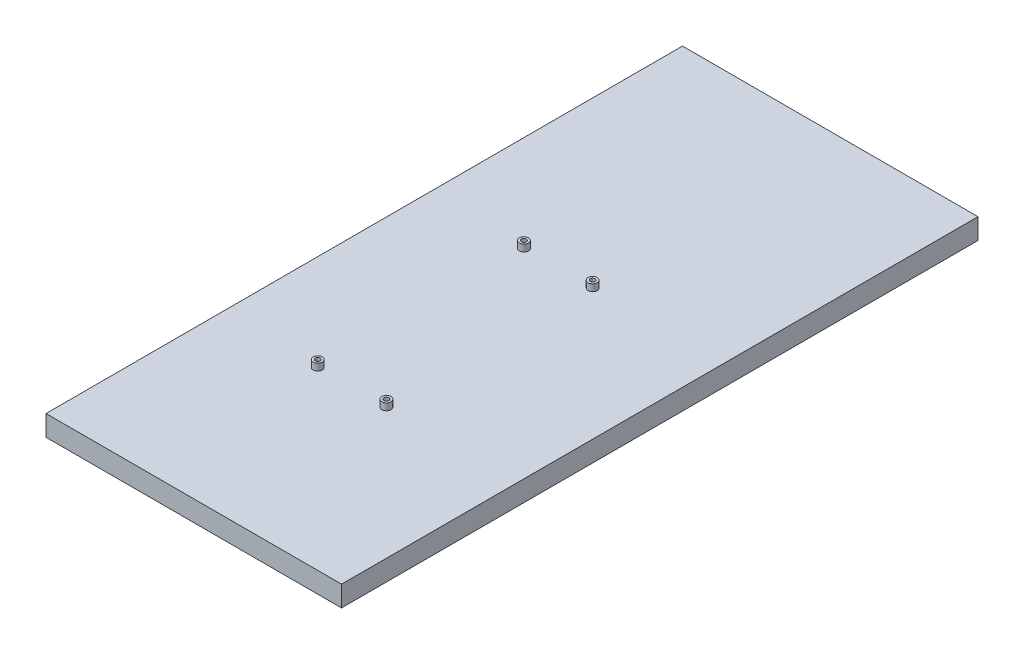
SolidWorks part; units mm, degrees
ref_plane "Front Plane" through (0, 0, 0) normal (0, 0, 1) x (1, 0, 0)
ref_plane "Top Plane" through (0, 0, 0) normal (0, 1, 0) x (1, 0, 0)
ref_plane "Right Plane" through (0, 0, 0) normal (1, 0, 0) x (0, 0, -1)
sketch "Sketch1" plane through (0, 0, 0) normal (0, 1, 0) x (1, 0, 0)
  line L1 (-215, -231.5) -> (215, -231.5)
  line L2 (-215, -231.5) -> (-215, 231.5)
  line L3 (-215, 231.5) -> (215, 231.5)
  line L4 (215, -231.5) -> (215, 231.5)
  line L5 (-215, -231.5) -> (215, 231.5) construction
  line L6 (-215, 231.5) -> (215, -231.5) construction
  point P0 (0, 0)
  dimension "D1" = 430
  dimension "D2" = 463
extrude "Boss-Extrude1" add sketch "Sketch1" along normal blind 15
sketch "Sketch6" plane through (0, 15, 0) normal (0, 1, 0) x (1, 0, 0)
  circle A0 centre (119.7933, 46.3731) radius 3.3
  circle A1 centre (69.7933, 46.3731) radius 3.3
  circle A2 centre (119.7933, -103.6269) radius 3.3
  circle A3 centre (69.7933, -103.6269) radius 3.3
sketch "Sketch7" plane through (0, 15, 0) normal (0, 1, 0) x (1, 0, 0)
  circle A0 centre (-116.3627, 94.9459) radius 3.3
  circle A1 centre (-55.3632, 95.1916) radius 3.3
  circle A2 centre (-54.9804, 0.1924) radius 3.3
  circle A3 centre (-115.98, -0.0534) radius 3.3
extrude "Boss-Extrude2" add sketch "Sketch7" along normal blind 5
sketch "Sketch8" plane through (0, 20, 0) normal (0, 1, 0) x (1, 0, 0)
  circle A0 centre (-54.9804, 0.1924) radius 1.75
  circle A1 centre (-55.3632, 95.1916) radius 1.75
  circle A2 centre (-116.3627, 94.9459) radius 1.75
  circle A3 centre (-115.98, -0.0534) radius 1.75
extrude "Cut-Extrude1" cut sketch "Sketch8" against normal blind 4
extrude "Boss-Extrude3" add sketch "Sketch6" along normal blind 5
sketch "Sketch10" plane through (0, 20, 0) normal (0, 1, 0) x (1, 0, 0)
  circle A0 centre (69.7933, 46.3731) radius 1.75
  circle A1 centre (119.7933, 46.3731) radius 1.75
  circle A2 centre (119.7933, -103.6269) radius 1.75
  circle A3 centre (69.7933, -103.6269) radius 1.75
extrude "Cut-Extrude2" cut sketch "Sketch10" against normal blind 4
sketch "Sketch12" plane through (0, 0, 0) normal (0, -1, 0) x (-1, 0, 0)
  circle A0 centre (-183.5287, -175) radius 3.8
  circle A1 centre (-203.3989, 170) radius 3.8
  circle A3 centre (-183.5287, 10) radius 3.8
  circle A4 centre (-203.3989, 10) radius 3.8
  circle A5 centre (-203.3989, -175) radius 3.8
  circle A6 centre (-183.5287, 170) radius 3.8
  circle A7 centre (206.5253, -175) radius 3.8
  circle A8 centre (206.5253, 20) radius 3.8
  circle A9 centre (186.4469, 175) radius 3.8
  circle A10 centre (206.5253, 175) radius 3.8
  circle A11 centre (186.4469, -175) radius 3.8
  circle A12 centre (186.4469, 20) radius 3.8
  circle A13 centre (160.3499, -221.5206) radius 3.8
  circle A14 centre (160.3499, -201.5484) radius 3.8
  circle A15 centre (20, -221.5206) radius 3.8
  circle A16 centre (20, -201.5484) radius 3.8
  circle A17 centre (-20, -201.5484) radius 3.8
  circle A19 centre (-20, -221.5206) radius 3.8
  circle A20 centre (-160, -221.5206) radius 3.8
  circle A21 centre (-160, -201.5484) radius 3.8
  circle A22 centre (160, 201.0677) radius 3.8
  circle A23 centre (160, 221.0364) radius 3.8
  circle A24 centre (20, 201.0677) radius 3.8
  circle A25 centre (20, 221.0364) radius 3.8
  circle A26 centre (-20, 201.0677) radius 3.8
  circle A27 centre (-20, 221.0364) radius 3.8
  circle A28 centre (-160, 201.0677) radius 3.8
  circle A29 centre (-160, 221.0364) radius 3.8
extrude "Cut-Extrude3" cut sketch "Sketch12" against normal blind 10
ref_plane "Plane1" through (0, 0, 0) normal (-1, 0, 0) x (0, 0, 1)
sketch "Sketch13" plane through (0, 0, 0) normal (-1, 0, 0) x (0, 0, 1)
  line L0 (-231.5, 15) -> (-231.5, 27.6364)
  line L1 (231.5, 15) -> (231.5, 28.0294)
  line L2 (231.5, 28.0294) -> (-231.5, 27.6364)
  line L4 (-231.5, 0) -> (231.5, 0)
  line L5 (231.5, 0) -> (231.5, 15)
  line L6 (231.5, 15) -> (-231.5, 15)
  line L7 (-231.5, 15) -> (-231.5, 0)
  line L8 (-231.5, 0) -> (231.5, 0)
  line L9 (231.5, 0) -> (231.5, 15)
  line L11 (-231.5, 15) -> (-231.5, 0)
  dimension "D1" = 0
extrude "Cut-Extrude4" cut sketch "Sketch13" along normal through all
